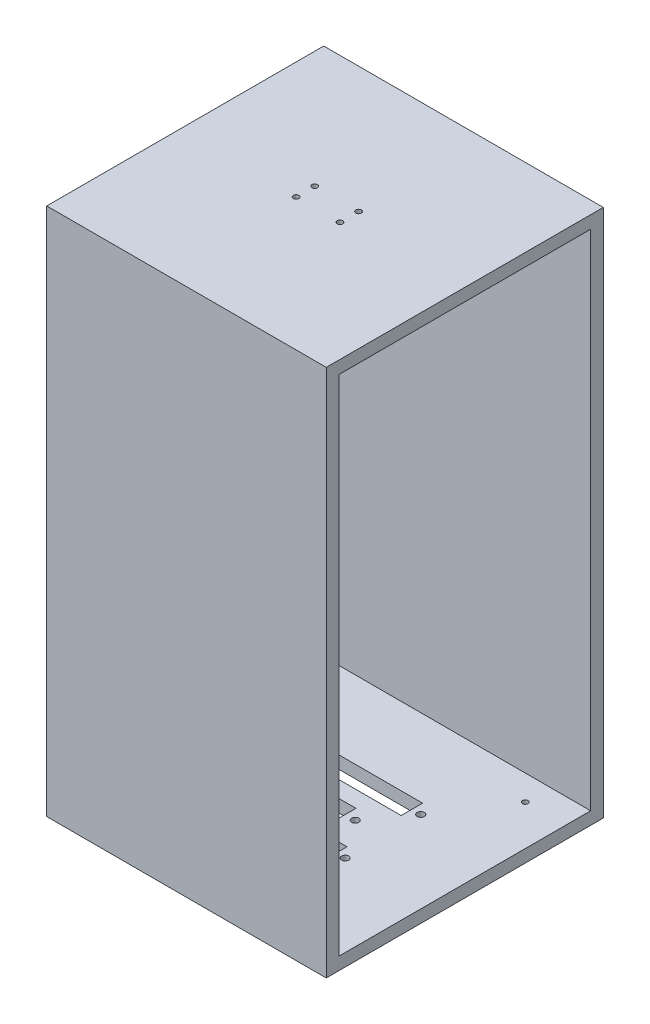
SolidWorks part; units mm, degrees
ref_plane "Front Plane" through (0, 0, 0) normal (0, 0, 1) x (1, 0, 0)
ref_plane "Top Plane" through (0, 0, 0) normal (0, 1, 0) x (1, 0, 0)
ref_plane "Right Plane" through (0, 0, 0) normal (1, 0, 0) x (0, 0, -1)
sketch "Sketch1" plane through (0, 0, 0) normal (0, 1, 0) x (1, 0, 0)
  line L5 (-55, 55) -> (56, 55)
  line L6 (-55, 55) -> (-55, -55)
  line L7 (-55, -55) -> (56, -55)
  line L8 (56, 55) -> (56, -55)
  dimension "D1" = 111
  dimension "D2" = 110
  dimension "D3" = 55
  dimension "D4" = 55
extrude "Main-Body" add sketch "Sketch1" along normal blind 210
sketch "Sketch2" plane through (0, 0, 0) normal (0, -1, 0) x (1, 0, 0)
  circle A0 centre (-40, 40) radius 1.1
  circle A1 centre (40, 40) radius 1.1
  circle A2 centre (40, -40) radius 1.1
  circle A3 centre (-40, -40) radius 1.1
  dimension "D1" = 40
  dimension "D3" = 2.2
  dimension "D2" = 40
  dimension "D4" = 2
  dimension "D5" = 2
shell "Hollow-Inside" thickness 5 removed face at (56, 105, 0)
extrude "Main-PCB-Holes" cut sketch "Sketch2" against normal up to next
sketch "Sketch3" plane through (0, 210, 0) normal (0, 1, 0) x (1, 0, 0)
  line L0 (-8.58, 5) -> (8.829, 5) construction
  circle A0 centre (-8.58, 5) radius 1.1
  circle A1 centre (8.829, 5) radius 1.1
  circle A2 centre (8.829, -2.4) radius 1.1
  circle A3 centre (-8.58, -2.4) radius 1.1
  dimension "D1" = 8.58
  dimension "D3" = 2.2
  dimension "D2" = 5
  dimension "D4" = 2
  dimension "D6" = 17.409
  dimension "D7" = 7.4
  dimension "D5" = 2
extrude "LED-PCB-Holes" cut sketch "Sketch3" against normal up to next
sketch "Sketch4" plane through (0, 0, 0) normal (0, -1, 0) x (1, 0, 0)
  line L0 (-12.4968, 0) -> (12.4968, 0) construction
  line L1 (-23.52, -15) -> (23.52, -15) construction
  line L2 (-8.55, -4.25) -> (8.55, -4.25)
  line L3 (-8.55, -4.25) -> (-8.55, 4.25)
  line L4 (-8.55, 4.25) -> (8.55, 4.25)
  line L5 (8.55, -4.25) -> (8.55, 4.25)
  line L6 (-20, -19.25) -> (20, -19.25)
  line L7 (-20, -19.25) -> (-20, -10.75)
  line L8 (-20, -10.75) -> (20, -10.75)
  line L9 (20, -19.25) -> (20, -10.75)
  line L10 (-23.52, 15) -> (23.52, 15) construction
  line L11 (-20, 10.75) -> (20, 10.75)
  line L12 (-20, 10.75) -> (-20, 19.25)
  line L13 (-20, 19.25) -> (20, 19.25)
  line L14 (20, 10.75) -> (20, 19.25)
  circle A0 centre (-12.4968, 0) radius 1.4224
  circle A1 centre (12.4968, 0) radius 1.4224
  circle A2 centre (-23.52, -15) radius 1.4224
  circle A3 centre (23.52, -15) radius 1.4224
  circle A4 centre (-23.52, 15) radius 1.4224
  circle A5 centre (23.52, 15) radius 1.4224
  point P4 (0, 0)
  point P6 (0, 0)
  point P7 (8.55, 0)
  point P12 (0, 4.25)
  point P17 (0, -15)
  point P22 (20, 15)
  point P23 (20, -15)
  point P24 (0, -19.25)
  point P29 (0, 15)
  point P35 (0, 10.75)
  dimension "D1" = 2.8448
  dimension "D2" = 2.8448
  dimension "D8" = 2.8448
  dimension "D7" = 2.8448
  dimension "D14" = 2.8448
  dimension "D15" = 2.8448
  dimension "D3" = 24.9936
  dimension "D4" = 17.1
  dimension "D5" = 8.5
  dimension "D9" = 47.04
  dimension "D10" = 40
  dimension "D11" = 8.5
  dimension "D13" = 15
  dimension "D16" = 47.04
  dimension "D17" = 8.5
  dimension "D19" = 15
  dimension "D20" = 40
extrude "Connector-Slots" cut sketch "Sketch4" against normal up to next
